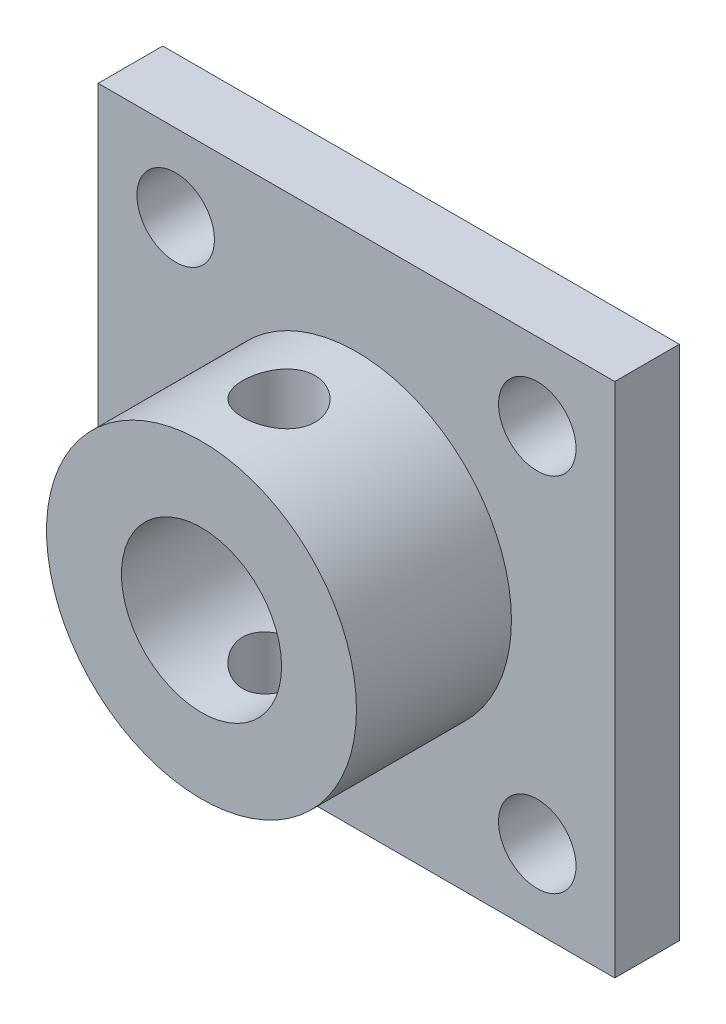
SolidWorks part; units mm, degrees
ref_plane "前视基准面" through (0, 0, 0) normal (0, 0, 1) x (1, 0, 0)
ref_plane "上视基准面" through (0, 0, 0) normal (0, 1, 0) x (1, 0, 0)
ref_plane "右视基准面" through (0, 0, 0) normal (1, 0, 0) x (0, 0, -1)
other "Configuration Table"
sketch "草图1" plane through (0, 0, 0) normal (0, 0, 1) x (1, 0, 0)
  line L1 (-10, 10) -> (10, 10)
  line L2 (-10, 10) -> (-10, -10)
  line L3 (-10, -10) -> (10, -10)
  line L4 (10, 10) -> (10, -10)
  line L5 (-10, 10) -> (10, -10) construction
  line L6 (-10, -10) -> (10, 10) construction
  circle A0 centre (-7, 7) radius 1.5
  circle A1 centre (7, 7) radius 1.5
  circle A2 centre (7, -7) radius 1.5
  circle A3 centre (-7, -7) radius 1.5
  circle A4 centre (0, 0) radius 3.1
  point P0 (0, 0)
  point P17 (0, 0)
  dimension "D3" = 3
  dimension "D5" = 6.2
  dimension "D1" = 20
  dimension "D2" = 20
  dimension "D4" = 4
extrude "凸台-拉伸1" add sketch "草图1" along normal blind 2.5
sketch "草图2" plane through (0, 0, 2.5) normal (0, 0, 1) x (1, 0, 0)
  circle A0 centre (0, 0) radius 3.1
  circle A1 centre (0, 0) radius 6
  dimension "D1" = 6.2
  dimension "D2" = 12
extrude "凸台-拉伸2" add sketch "草图2" along normal blind 6
sketch "草图3" plane through (0, 0, 0) normal (0, 1, 0) x (1, 0, 0)
  line L0 (-6, -5.5) -> (6, -5.5) construction
  line L1 (-6, -2.5) -> (-6, -8.5) construction
  line L2 (6, -8.5) -> (6, -2.5) construction
  circle A0 centre (0, -5.5) radius 1.4
  dimension "D1" = 2.8
extrude "切除-拉伸1" cut sketch "草图3" against normal through all both and the other way through all
